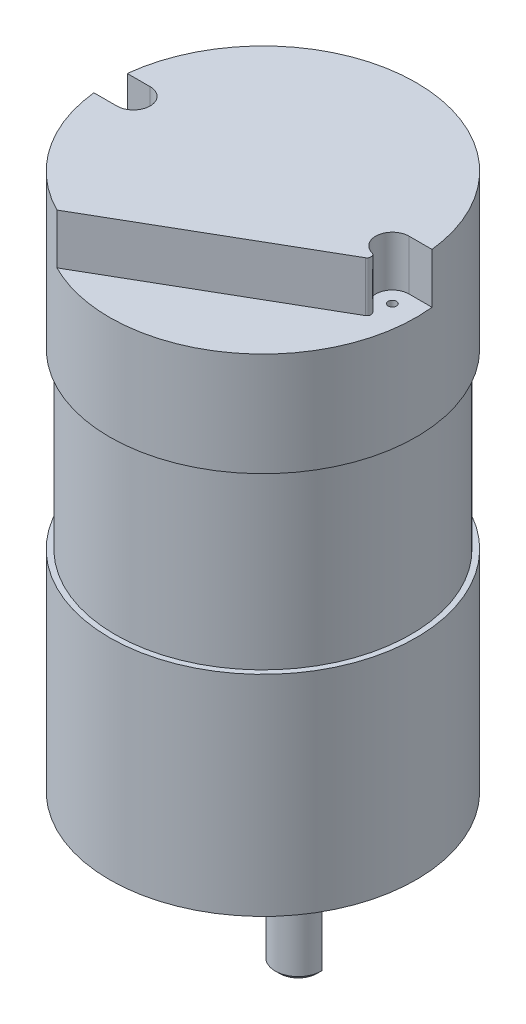
SolidWorks part; units mm, degrees
material "PE High Density"
ref_plane "Front Plane" through (0, 0, 0) normal (0, 0, 1) x (1, 0, 0)
ref_plane "Top Plane" through (0, 0, 0) normal (0, 1, 0) x (1, 0, 0)
ref_plane "Right Plane" through (0, 0, 0) normal (1, 0, 0) x (0, 0, -1)
sketch "Sketch1" plane through (0, 0, 0) normal (0, 0, 1) x (1, 0, 0)
  line L0 (0, 41.1329) -> (0, -49.1088) construction
  line L1 (0, 32.15) -> (18.35, 32.15)
  line L2 (18.35, 32.15) -> (18.35, 13.75)
  line L3 (18.35, 13.75) -> (17.7, 13.75)
  line L4 (17.7, 13.75) -> (17.7, -7.05)
  line L5 (17.7, -7.05) -> (18.35, -7.05)
  line L6 (18.35, -7.05) -> (18.35, -32.15)
  line L7 (18.35, -32.15) -> (0, -32.15)
  line L8 (0, 32.15) -> (0, -32.15)
  point P11 (0, 0)
  dimension "D1" = 36.7
  dimension "D2" = 18.4
  dimension "D3" = 35.4
  dimension "D4" = 25.1
  dimension "D5" = 64.3
revolve "Revolve1" add sketch "Sketch1" angle 360 about L0
sketch "Sketch2" plane through (0, 32.15, 0) normal (0, 1, 0) x (1, 0, 0)
  line L0 (-18.35, 0) -> (18.35, 0) construction
  line L1 (-15.5, 0) -> (-20.9613, 0) construction
  line L2 (-15.5, -2) -> (-20.9613, -2)
  line L3 (-15.5, 2) -> (-20.9613, 2)
  line L4 (15.4931, 0) -> (18.35, 0) construction
  line L5 (15.4931, 2) -> (18.35, 2)
  line L6 (15.4931, -2) -> (18.35, -2)
  line L7 (-8.2957, -16.3678) -> (18.3228, -0.9996)
  circle A0 centre (0, 0) radius 18.35 construction
  circle A1 centre (0, 0) radius 15.5 construction
  arc A2 (-15.5, -2) -> (-15.5, 2) centre (-15.5, 0) ccw
  arc A3 (-20.9613, 2) -> (-20.9613, -2) centre (-20.9613, 0) ccw
  arc A4 (15.4931, 2) -> (15.4931, -2) centre (15.4931, 0) ccw
  arc A5 (18.35, -2) -> (18.35, 2) centre (18.35, 0) ccw
  arc A6 (-8.2957, -16.3678) -> (18.3202, -1.0461) centre (0, 0) ccw
  point P10 (-18.2306, 0)
  point P16 (16.9216, 0)
  circle M3 centre (0, 0) radius 18.35
  dimension "D1" = 31
  dimension "D2" = 2
  dimension "D3" = 2
  dimension "D4" = 30
  dimension "D5" = 1
extrude "Cut-Extrude3" cut sketch "Sketch2" against normal blind 6 contours L2 A2 L3 M3 | L5 A4 L6 L7 M3 | L7 L6 M3 | L7 L6 M3 region at (-16.0988, 32.15, 0) region at (6.6645, 32.15, 11.6776) region at (16.0148, 32.15, -0.0826) region at (17.721, 32.15, 1.6656)
fillet "Fillet1" radius 0.5 1 edges at (16.5901, 29.15, 2)
sketch "Sketch3" plane through (0, 26.15, 0) normal (0, 1, 0) x (1, 0, 0)
  circle A0 centre (15.4931, 0) radius 0.5
  circle A1 centre (-15.4331, 0) radius 0.5
  dimension "D1" = 1
extrude "Cut-Extrude4" cut sketch "Sketch3" against normal up to surface (33.2 mm away) up to face at (0, -7.05, 17.7)
sketch "Sketch4" plane through (0, -32.15, 0) normal (0, -1, 0) x (1, 0, 0)
  line L0 (-2.3235, -6.5501) -> (3.409, 9.6101) construction
  line L4 (15.1136, 2.8524) -> (-8.2957, 16.3678)
  line L5 (18.2407, -2) -> (15.4931, -2)
  line L6 (-15.5, -2) -> (-18.2407, -2)
  line L7 (-18.2407, 2) -> (-15.5, 2)
  line L8 (15.1136, 2.8524) -> (-8.2957, 16.3678) construction
  line L9 (18.2407, -2) -> (15.4931, -2)
  line L10 (-15.5, -2) -> (-18.2407, -2) construction
  line L11 (-18.2407, 2) -> (-15.5, 2) construction
  circle A0 centre (0, 0) radius 1.05 construction
  circle A1 centre (0, 0) radius 18.35 construction
  circle A2 centre (0, 0) radius 6.95 construction
  circle A3 centre (-2.3235, -6.5501) radius 5.95
  circle A4 centre (0, 0) radius 18.35
  arc A8 (14.9895, 1.9355) -> (15.1136, 2.8524) centre (14.8636, 2.4194) ccw
  arc A9 (14.9895, 1.9355) -> (15.4931, -2) centre (15.4931, 0) ccw
  arc A10 (-18.2407, -2) -> (18.2407, -2) centre (0, 0) ccw
  arc A11 (-15.5, -2) -> (-15.5, 2) centre (-15.5, 0) ccw
  arc A12 (-8.2957, 16.3678) -> (-18.2407, 2) centre (0, 0) ccw
  arc A13 (14.9895, 1.9355) -> (15.1136, 2.8524) centre (14.8636, 2.4194) ccw construction
  arc A14 (14.9895, 1.9355) -> (15.4931, -2) centre (15.4931, 0) ccw construction
  arc A15 (-18.2407, -2) -> (18.2407, -2) centre (0, 0) ccw construction
  arc A16 (-15.5, -2) -> (-15.5, 2) centre (-15.5, 0) ccw construction
  arc A17 (-8.2957, 16.3678) -> (-18.2407, 2) centre (0, 0) ccw construction
  dimension "D1" = 17.3
  dimension "D4" = 11.9
  dimension "D2" = 5.9
  dimension "D3" = 0
extrude "Boss-Extrude1" add sketch "Sketch4" along normal blind 6 contours A3 region at (-2.3235, -32.15, -6.5501)
sketch "Sketch5" plane through (0, -38.15, 0) normal (0, -1, 0) x (1, 0, 0)
  circle A0 centre (-2.3235, -6.5501) radius 2.75
  dimension "D1" = 5.5
extrude "Boss-Extrude2" add sketch "Sketch5" along normal blind 16.2
chamfer "Chamfer1" distance 0.5 angle 45 1 edges at (-2.3235, -54.35, -9.3001)
sketch "Sketch7" plane through (0, -54.35, 0) normal (0, -1, 0) x (1, 0, 0)
  line L0 (-2.3558, -9.2999) -> (0.4249, -6.6455)
  line L1 (0.4249, -6.6455) -> (1.7515, -8.0352)
  line L2 (1.7515, -8.0352) -> (-1.0292, -10.6896)
  line L3 (-1.0292, -10.6896) -> (-2.3558, -9.2999)
  circle A0 centre (-2.3235, -6.5501) radius 2.75 construction
  circle A1 centre (-2.3235, -6.5501) radius 2.75 construction
extrude "Cut-Extrude5" cut sketch "Sketch7" against normal blind 12
sketch "Sketch8" plane through (0, -32.15, 0) normal (0, -1, 0) x (1, 0, 0)
  arc A0 (1.7846, -10.8543) -> (-8.2256, -7.3034) centre (0, 0) ccw construction
  circle A1 centre (-2.3235, -6.5501) radius 5.95 construction
  arc A2 (1.7846, -10.8543) -> (-8.2256, -7.3034) centre (-2.3235, -6.5501) ccw construction
  arc A3 (-9.4584, -4.0812) -> (4.7724, -9.1292) centre (-2.3235, -6.5501) cw
  arc A4 (5.3426, -9.6155) -> (-10.2076, -4.0994) centre (0, 0) ccw
  arc A5 (4.7724, -9.1292) -> (5.3426, -9.6155) centre (5.1483, -9.2658) ccw
  arc A6 (-9.4584, -4.0812) -> (-10.2076, -4.0994) centre (-9.8364, -3.9504) cw
  point P10 (4.3346, -10.11)
  point P13 (-9.7365, -5.1186)
  dimension "D1" = 22
  dimension "D2" = 1.6
  dimension "D3" = 0.4
extrude "Cut-Extrude6" cut sketch "Sketch8" against normal blind 0.8 contours A3 A4 region at (1.0228, -32.15, 2.8835)
sketch "Sketch9" plane through (0, -32.15, 0) normal (0, -1, 0) x (1, 0, 0)
  line L0 (0, 0) -> (-3.3343, 18.0445) construction
  line L1 (-2.3235, -6.5501) -> (5.0983, 14.3725) construction
  circle A0 centre (0, 0) radius 18.35 construction
  circle A1 centre (0, 0) radius 15.25 construction
  circle A2 centre (0, 15.25) radius 1.5 construction
  circle A3 centre (-2.771, 14.9961) radius 1.5
  circle A4 centre (11.6015, 9.8978) radius 1.5
  circle A5 centre (14.3725, -5.0983) radius 1.5
  circle A6 centre (2.771, -14.9961) radius 1.5
  circle A7 centre (-11.6015, -9.8978) radius 1.5
  circle A8 centre (-14.3725, 5.0983) radius 1.5
  point P27 (0, 0)
  dimension "D1" = 30.5
  dimension "D2" = 3
  dimension "D3" = 30
  dimension "D4" = 6
extrude "Cut-Extrude7" cut sketch "Sketch9" against normal blind 3.2
fillet "Fillet2" radius 0.5 4 edges at (4.8887, -31.35, -9.5702) (0.2006, -31.35, 0.5655) (-9.8266, -31.35, -4.3502) (3.6775, -31.35, 10.3671)
